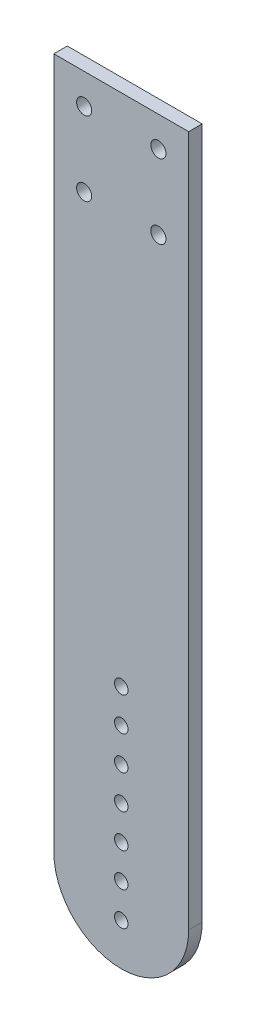
SolidWorks part; units mm, degrees
other "Markup1"
sketch "Sketch7" plane through (-20, 225, -2) normal (-0.1146, 0.1086, -0.9875) x (-0.991, 0.0573, 0.1213)
ref_plane "Front Plane" through (0, 0, 0) normal (0, 0, 1) x (1, 0, 0)
ref_plane "Top Plane" through (0, 0, 0) normal (0, 1, 0) x (1, 0, 0)
ref_plane "Right Plane" through (0, 0, 0) normal (1, 0, 0) x (0, 0, -1)
sketch "Sketch1" plane through (0, 0, 0) normal (0, 1, 0) x (1, 0, 0)
  line L1 (-20, 2) -> (20, 2)
  line L2 (-20, 2) -> (-20, -2)
  line L3 (-20, -2) -> (20, -2)
  line L4 (20, 2) -> (20, -2)
  line L5 (-20, 2) -> (20, -2) construction
  line L6 (-20, -2) -> (20, 2) construction
  point P0 (0, 0)
extrude "Boss-Extrude1" add sketch "Sketch1" along normal blind 225
fillet "Fillet1" radius 20 2 edges at (-20, 0, 0) (20, 0, 0)
sketch "Sketch2" plane through (0, 0, 2) normal (0, 0, 1) x (1, 0, 0)
  circle A0 centre (0, 12.5) radius 2
  dimension "D1" = 12.5
extrude "Cut-Extrude1" cut sketch "Sketch2" against normal through all
pattern_linear "LPattern1" count 7 spacing 10 along (0, 1, 0) of "Cut-Extrude1"
sketch "Sketch8" plane through (0, 0, -2) normal (0, 0, -1) x (-1, 0, 0)
  line L0 (-20, 225) -> (20, 225) construction
  line L1 (-20, 225) -> (-20, 20) construction
  line L2 (20, 225) -> (20, 20) construction
  line L3 (-20, 185) -> (20, 185) construction
  circle A0 centre (-11, 216) radius 2.25
  circle A1 centre (11, 216) radius 2.25
  circle A2 centre (-11, 194) radius 2.25
  circle A3 centre (11, 194) radius 2.25
  dimension "D1" = 9
  dimension "D3" = 9
  dimension "D5" = 4.5
  dimension "D2" = 9
  dimension "D4" = 9
  dimension "D6" = 40
  dimension "D7" = 9
extrude "Cut-Extrude4" cut sketch "Sketch8" against normal through all
